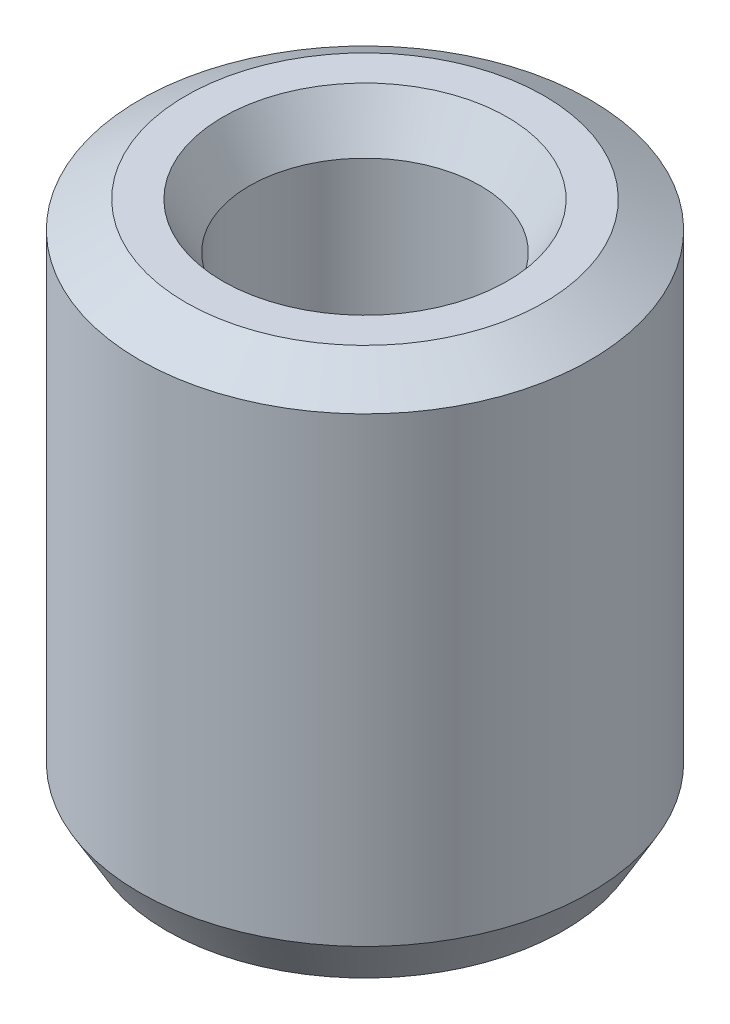
SolidWorks part; units mm, degrees
ref_plane "Front Plane" through (0, 0, 0) normal (0, 0, 1) x (1, 0, 0)
ref_plane "Top Plane" through (0, 0, 0) normal (0, 1, 0) x (1, 0, 0)
ref_plane "Right Plane" through (0, 0, 0) normal (1, 0, 0) x (0, 0, -1)
sketch "Sketch1" plane through (0, 0, 0) normal (0, 1, 0) x (1, 0, 0)
  circle A0 centre (0, 0) radius 10
  dimension "SLEEVE_OD" = 20
extrude "Boss-Extrude1" add sketch "Sketch1" along normal blind 23.7035
sketch "Sketch2" plane through (0, 0, 0) normal (0, 1, 0) x (1, 0, 0)
  circle A0 centre (0, 0) radius 5.1283
  dimension "BORE_D" = 10.2567
extrude "Cut-Extrude1" cut sketch "Sketch2" along normal through all
chamfer "Chamfer1" distance 1.1839 angle 60 4 edges at (0, 23.7035, 5.1283) (0, 0, 5.1283) (0, 0, 10) (0, 23.7035, 10) first distance on face at (0, 23.7035, 5.1283) first distance on face at (0, 0, 5.1283) first distance on face at (0, 23.7035, 10)
